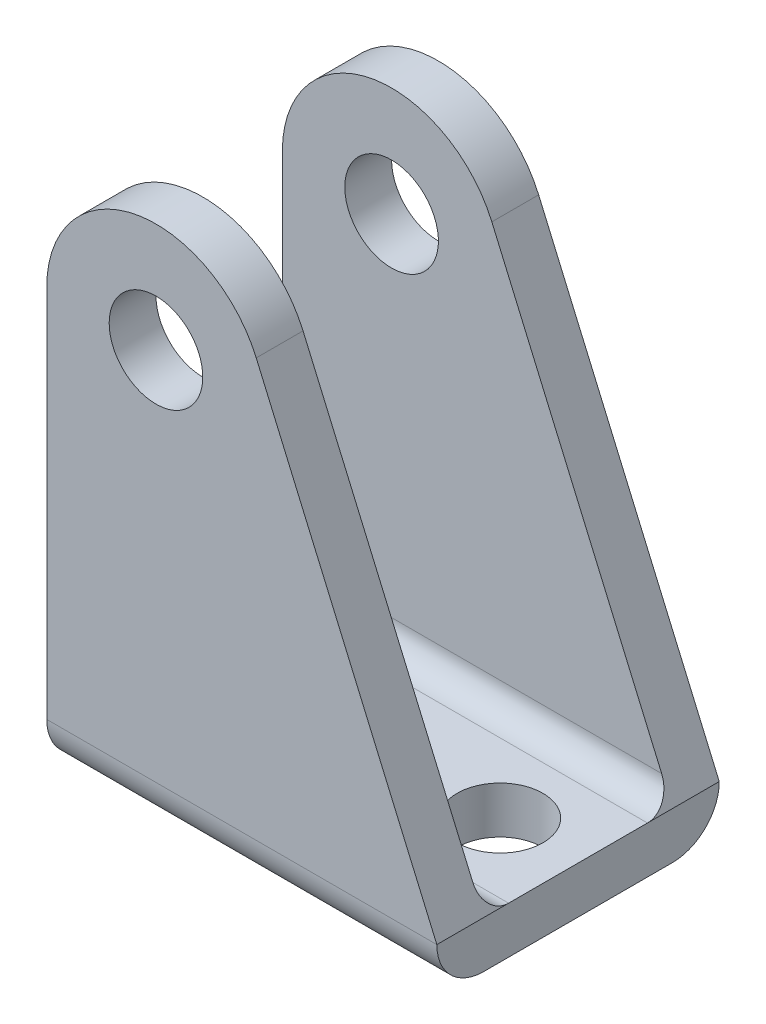
SolidWorks part; units mm, degrees
ref_plane "Front Plane" through (0, 0, 0) normal (0, 0, 1) x (1, 0, 0)
ref_plane "Top Plane" through (0, 0, 0) normal (0, 1, 0) x (1, 0, 0)
ref_plane "Right Plane" through (0, 0, 0) normal (1, 0, 0) x (0, 0, -1)
ref_plane "Plane1" through (0, 0, 0) normal (1, 0, 0) x (0, 0, -1)
sketch "Sketch1" plane through (0, 0, 0) normal (1, 0, 0) x (0, 0, -1)
  line L0 (-6.05, 0) -> (6.05, 0)
  line L1 (9.05, 3) -> (9.05, 34)
  line L2 (9.05, 34) -> (6.05, 34)
  line L3 (6.05, 34) -> (6.05, 4.6)
  line L4 (4.45, 3) -> (-4.45, 3)
  line L5 (-6.05, 4.6) -> (-6.05, 34)
  line L6 (-6.05, 34) -> (-9.05, 34)
  line L7 (-9.05, 34) -> (-9.05, 3)
  arc A0 (-9.05, 3) -> (-6.05, 0) centre (-6.05, 3) ccw
  arc A1 (6.05, 0) -> (9.05, 3) centre (6.05, 3) ccw
  arc A2 (6.05, 4.6) -> (4.45, 3) centre (4.45, 4.6) cw
  arc A3 (-4.45, 3) -> (-6.05, 4.6) centre (-4.45, 4.6) cw
extrude "Boss-Extrude1" add sketch "Sketch1" against normal blind 25 and the other way blind 25
ref_plane "Plane2" through (0, 0, 0) normal (0, 0, 1) x (1, 0, 0)
sketch "Sketch2" plane through (0, 0, 0) normal (0, 0, 1) x (1, 0, 0)
  line L0 (-37.1, 54) -> (-37.1, -12.1)
  line L1 (-37.1, -12.1) -> (37.1, -12.1)
  line L2 (37.1, -12.1) -> (37.1, 54)
  line L3 (37.1, 54) -> (-37.1, 54)
  line L4 (0, 0) -> (25, 0)
  line L5 (25, 0) -> (25, 3)
  line L6 (25, 3) -> (13.4254, 29.7774)
  line L7 (0, 27) -> (0, 0)
  arc A0 (13.4254, 29.7774) -> (0, 27) centre (7, 27) ccw
extrude "Cut-Extrude1" cut sketch "Sketch2" against normal blind 25 and the other way blind 25
ref_plane "Plane3" through (0, 0, 0) normal (0, 0, 1) x (1, 0, 0)
sketch "Sketch3" plane through (0, 0, 0) normal (0, 0, 1) x (1, 0, 0)
  circle A0 centre (7, 27) radius 3
extrude "Cut-Extrude2" cut sketch "Sketch3" against normal blind 12.1 and the other way blind 12.1
ref_plane "Plane4" through (0, 0, 0) normal (0, 1, 0) x (1, 0, 0)
sketch "Sketch4" plane through (0, 0, 0) normal (0, 1, 0) x (1, 0, 0)
  circle A0 centre (5, 0) radius 2.75
extrude "Cut-Extrude3" cut sketch "Sketch4" against normal blind 3 and the other way blind 3
ref_plane "Plane5" through (0, 0, 0) normal (0, 1, 0) x (1, 0, 0)
sketch "Sketch5" plane through (0, 0, 0) normal (0, 1, 0) x (1, 0, 0)
  circle A0 centre (20, 0) radius 2.75
extrude "Cut-Extrude4" cut sketch "Sketch5" against normal blind 3 and the other way blind 3
